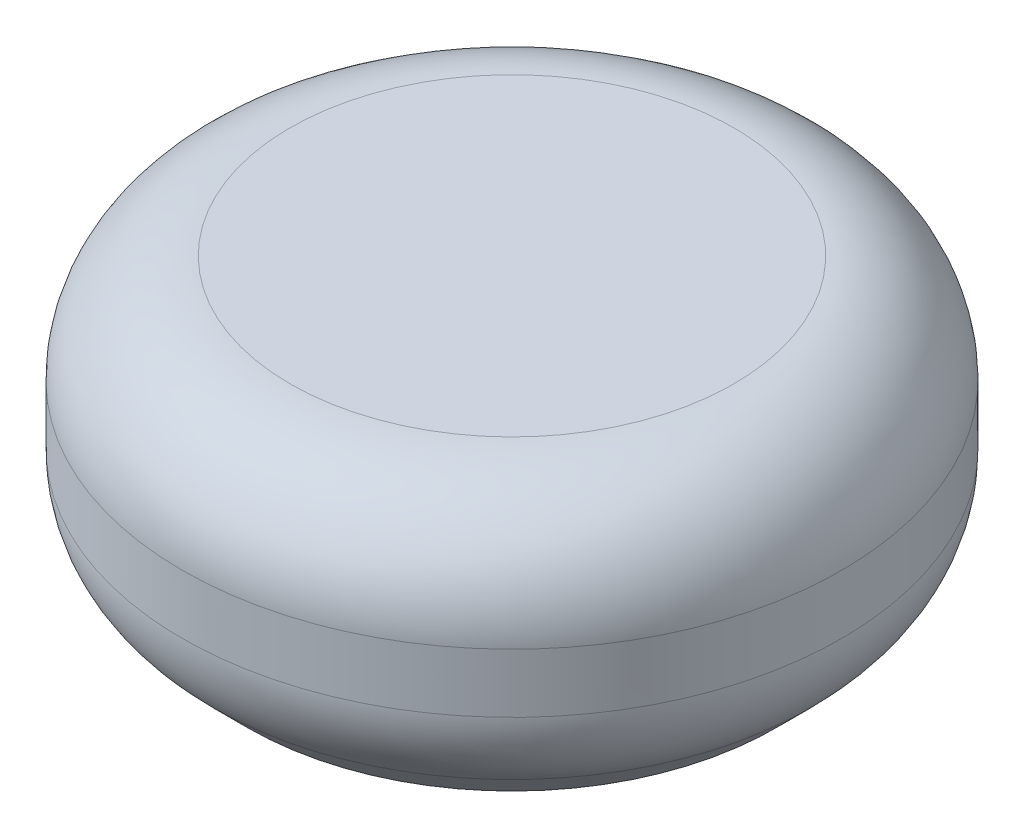
SolidWorks part; units mm, degrees
ref_plane "Front Plane" through (0, 0, 0) normal (0, 0, 1) x (1, 0, 0)
ref_plane "Top Plane" through (0, 0, 0) normal (0, 1, 0) x (1, 0, 0)
ref_plane "Right Plane" through (0, 0, 0) normal (1, 0, 0) x (0, 0, -1)
sketch "Sketch1" plane through (0, 0, 0) normal (0, 1, 0) x (1, 0, 0)
  circle A0 centre (0, 0) radius 15.5625
  circle A1 centre (0, 0) radius 19.431
  dimension "D1" = 31.125
  dimension "D2" = 38.862
extrude "Boss-Extrude1" add sketch "Sketch1" along normal blind 15
sketch "Sketch2" plane through (0, 15, 0) normal (0, 1, 0) x (1, 0, 0)
  circle A0 centre (0, 0) radius 19.431
  dimension "D1" = 38.862
extrude "Boss-Extrude2" add sketch "Sketch2" along normal blind 3.81
fillet "Fillet1" radius 6.35 1 edges at (0, 18.81, 19.431)
chamfer "Chamfer1" distance 6.35 angle 45 1 edges at (0, 0, 19.431)
fillet "Fillet2" radius 6.35 1 edges at (0, 6.35, 19.431)
